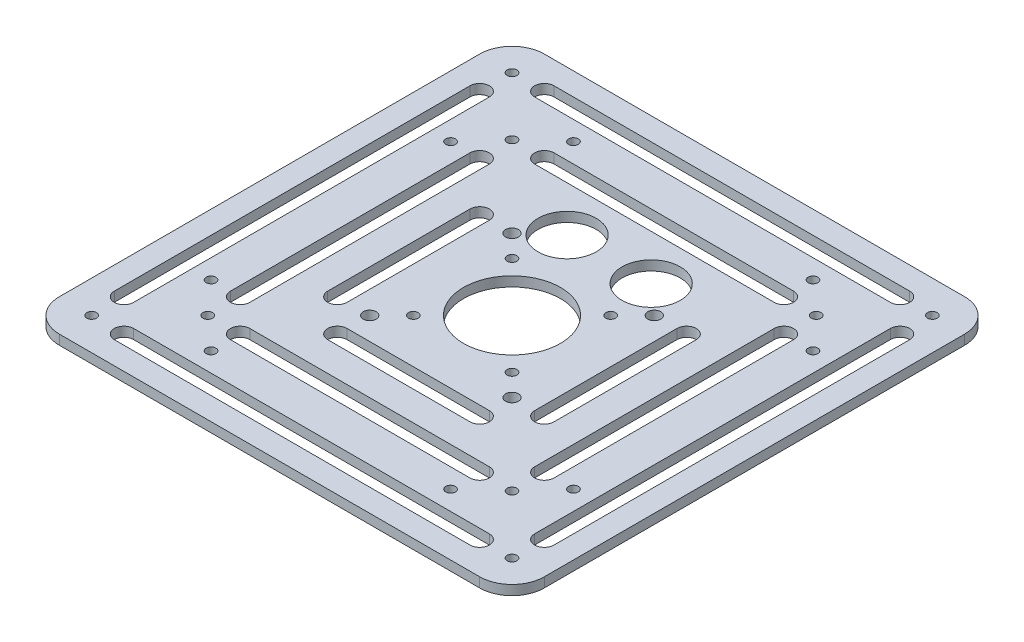
SolidWorks part; units mm, degrees
ref_plane "Front Plane" through (0, 0, 0) normal (0, 0, 1) x (1, 0, 0)
ref_plane "Top Plane" through (0, 0, 0) normal (0, 1, 0) x (1, 0, 0)
ref_plane "Right Plane" through (0, 0, 0) normal (1, 0, 0) x (0, 0, -1)
sketch "Sketch1" plane through (0, 0, 0) normal (0, 1, 0) x (1, 0, 0)
  line L0 (0, 0) -> (0, 75) construction
  line L1 (-65, -75) -> (65, -75)
  line L2 (-75, -65) -> (-75, 65)
  line L3 (-65, 75) -> (65, 75)
  line L4 (75, -65) -> (75, 65)
  line L5 (-75, -75) -> (75, 75) construction
  line L6 (-75, 75) -> (75, -75) construction
  line L7 (0, 0) -> (0, -75) construction
  line L8 (0, 0) -> (75, 0) construction
  line L9 (0, 0) -> (-75, 0) construction
  line L10 (-47.0395, 37.0395) -> (-47.0395, -37.0395) construction
  line L11 (-44.0395, 37.0395) -> (-44.0395, -37.0395)
  line L12 (-50.0395, 37.0395) -> (-50.0395, -37.0395)
  line L13 (47.0395, 37.0395) -> (47.0395, -37.0395) construction
  line L14 (44.0395, 37.0395) -> (44.0395, -37.0395)
  line L15 (50.0395, 37.0395) -> (50.0395, -37.0395)
  line L16 (-37.0395, 47.0395) -> (37.0395, 47.0395) construction
  line L17 (-37.0395, 44.0395) -> (37.0395, 44.0395)
  line L18 (-37.0395, 50.0395) -> (37.0395, 50.0395)
  line L19 (37.0395, -47.0395) -> (-37.0395, -47.0395) construction
  line L20 (37.0395, -44.0395) -> (-37.0395, -44.0395)
  line L21 (37.0395, -50.0395) -> (-37.0395, -50.0395)
  line L22 (-65, 55) -> (-65, -55) construction
  line L23 (-62, 55) -> (-62, -55)
  line L24 (-68, 55) -> (-68, -55)
  line L25 (65, 55) -> (65, -55) construction
  line L26 (62, 55) -> (62, -55)
  line L27 (68, 55) -> (68, -55)
  line L28 (-55, 65) -> (55, 65) construction
  line L29 (-55, 62) -> (55, 62)
  line L30 (-55, 68) -> (55, 68)
  line L31 (55, -65) -> (-55, -65) construction
  line L32 (55, -62) -> (-55, -62)
  line L33 (55, -68) -> (-55, -68)
  line L34 (-55, -65) -> (-37.0395, -47.0395) construction
  line L35 (37.0395, -47.0395) -> (55, -65) construction
  line L36 (-22, -32) -> (22, -32) construction
  line L37 (-22, -29) -> (22, -29)
  line L38 (-22, -35) -> (22, -35)
  line L39 (-32, -22) -> (-32, 22) construction
  line L40 (-29, -22) -> (-29, 22)
  line L41 (-35, -22) -> (-35, 22)
  line L42 (32, 22) -> (32, -22) construction
  line L43 (29, 22) -> (29, -22)
  line L44 (35, 22) -> (35, -22)
  arc A0 (-65, -75) -> (-75, -65) centre (-65, -65) cw
  arc A1 (65, -75) -> (75, -65) centre (65, -65) ccw
  arc A2 (65, 75) -> (75, 65) centre (65, 65) cw
  arc A3 (-75, 65) -> (-65, 75) centre (-65, 65) cw
  circle A4 centre (65, 65) radius 1.5
  circle A5 centre (47.0395, 47.0395) radius 1.5
  circle A6 centre (-65, 65) radius 1.5
  circle A7 centre (-47.0395, 47.0395) radius 1.5
  circle A8 centre (65, -65) radius 1.5
  circle A9 centre (47.0395, -47.0395) radius 1.5
  circle A10 centre (-65, -65) radius 1.5
  circle A11 centre (-47.0395, -47.0395) radius 1.5
  circle A12 centre (0, 0) radius 15
  arc A13 (-44.0395, 37.0395) -> (-50.0395, 37.0395) centre (-47.0395, 37.0395) ccw
  arc A14 (-50.0395, -37.0395) -> (-44.0395, -37.0395) centre (-47.0395, -37.0395) ccw
  arc A15 (44.0395, 37.0395) -> (50.0395, 37.0395) centre (47.0395, 37.0395) cw
  arc A16 (50.0395, -37.0395) -> (44.0395, -37.0395) centre (47.0395, -37.0395) cw
  arc A17 (-37.0395, 44.0395) -> (-37.0395, 50.0395) centre (-37.0395, 47.0395) cw
  arc A18 (37.0395, 50.0395) -> (37.0395, 44.0395) centre (37.0395, 47.0395) cw
  arc A19 (37.0395, -44.0395) -> (37.0395, -50.0395) centre (37.0395, -47.0395) cw
  arc A20 (-37.0395, -50.0395) -> (-37.0395, -44.0395) centre (-37.0395, -47.0395) cw
  arc A21 (-62, 55) -> (-68, 55) centre (-65, 55) ccw
  arc A22 (-68, -55) -> (-62, -55) centre (-65, -55) ccw
  arc A23 (62, 55) -> (68, 55) centre (65, 55) cw
  arc A24 (68, -55) -> (62, -55) centre (65, -55) cw
  arc A25 (-55, 62) -> (-55, 68) centre (-55, 65) cw
  arc A26 (55, 68) -> (55, 62) centre (55, 65) cw
  arc A27 (55, -62) -> (55, -68) centre (55, -65) cw
  arc A28 (-55, -68) -> (-55, -62) centre (-55, -65) cw
  circle A29 centre (-56.0395, 37.0395) radius 1.5
  circle A30 centre (-56.0395, -37.0395) radius 1.5
  circle A31 centre (56.0395, -37.0395) radius 1.5
  circle A32 centre (56.0395, 37.0395) radius 1.5
  circle A33 centre (-37.0395, 56.0395) radius 1.5
  circle A34 centre (37.0395, 56.0395) radius 1.5
  circle A35 centre (-37.0395, -56.0395) radius 1.5
  circle A36 centre (37.0395, -56.0395) radius 1.5
  circle A37 centre (-15.25, 15.25) radius 1.5
  circle A38 centre (15.25, 15.25) radius 1.5
  circle A39 centre (-15.25, -15.25) radius 1.5
  circle A40 centre (15.25, -15.25) radius 1.5
  circle A41 centre (-13, 30.0395) radius 9
  circle A42 centre (13, 30.0395) radius 9
  circle A43 centre (-22, 22) radius 2
  circle A44 centre (22, 22) radius 2
  circle A45 centre (22, -22) radius 2
  circle A46 centre (-22, -22) radius 2
  arc A47 (-22, -29) -> (-22, -35) centre (-22, -32) ccw
  arc A48 (22, -35) -> (22, -29) centre (22, -32) ccw
  arc A49 (-29, -22) -> (-35, -22) centre (-32, -22) cw
  arc A50 (-35, 22) -> (-29, 22) centre (-32, 22) cw
  arc A51 (29, 22) -> (35, 22) centre (32, 22) cw
  arc A52 (35, -22) -> (29, -22) centre (32, -22) cw
  point P0 (0, 0)
  point P38 (-47.0395, 0)
  point P45 (47.0395, 0)
  point P52 (0, 47.0395)
  point P59 (0, -47.0395)
  point P66 (-65, 0)
  point P73 (65, 0)
  point P80 (0, 65)
  point P87 (0, -65)
  point P134 (0, -32)
  point P141 (-32, 0)
  point P148 (32, 0)
  dimension "D3" = 10
  dimension "D4" = 3
  dimension "D7" = 3
  dimension "D11" = 30
  dimension "D13" = 10
  dimension "D16" = 10
  dimension "D18" = 9
  dimension "D21" = 3
  dimension "D22" = 3
  dimension "D24" = 3
  dimension "D25" = 3
  dimension "D26" = 3
  dimension "D27" = 18
  dimension "D30" = 74.079
  dimension "D31" = 5.9605
  dimension "D33" = 10
  dimension "D34" = 4
  dimension "D37" = 3
  dimension "D1" = 150
  dimension "D2" = 150
  dimension "D5" = 10
  dimension "D6" = 10
  dimension "D8" = 25.4
  dimension "D9" = 94.079
  dimension "D10" = 10
  dimension "D12" = 27.9605
  dimension "D14" = 10
  dimension "D15" = 27.9605
  dimension "D17" = 10
  dimension "D19" = 10
  dimension "D20" = 9
  dimension "D23" = 15.25
  dimension "D28" = 13
  dimension "D29" = 17
  dimension "D32" = 112.079
  dimension "D35" = 22
  dimension "D36" = 44
  dimension "D38" = 40
extrude "Boss-Extrude1" add sketch "Sketch1" along normal blind 3
sketch "Sketch2" plane through (0, 3, 0) normal (0, 1, 0) x (1, 0, 0)
sketch "Sketch3" plane through (0, 3, 0) normal (0, 1, 0) x (1, 0, 0)
sketch "Sketch4" plane through (0, 3, 0) normal (0, 1, 0) x (1, 0, 0)
